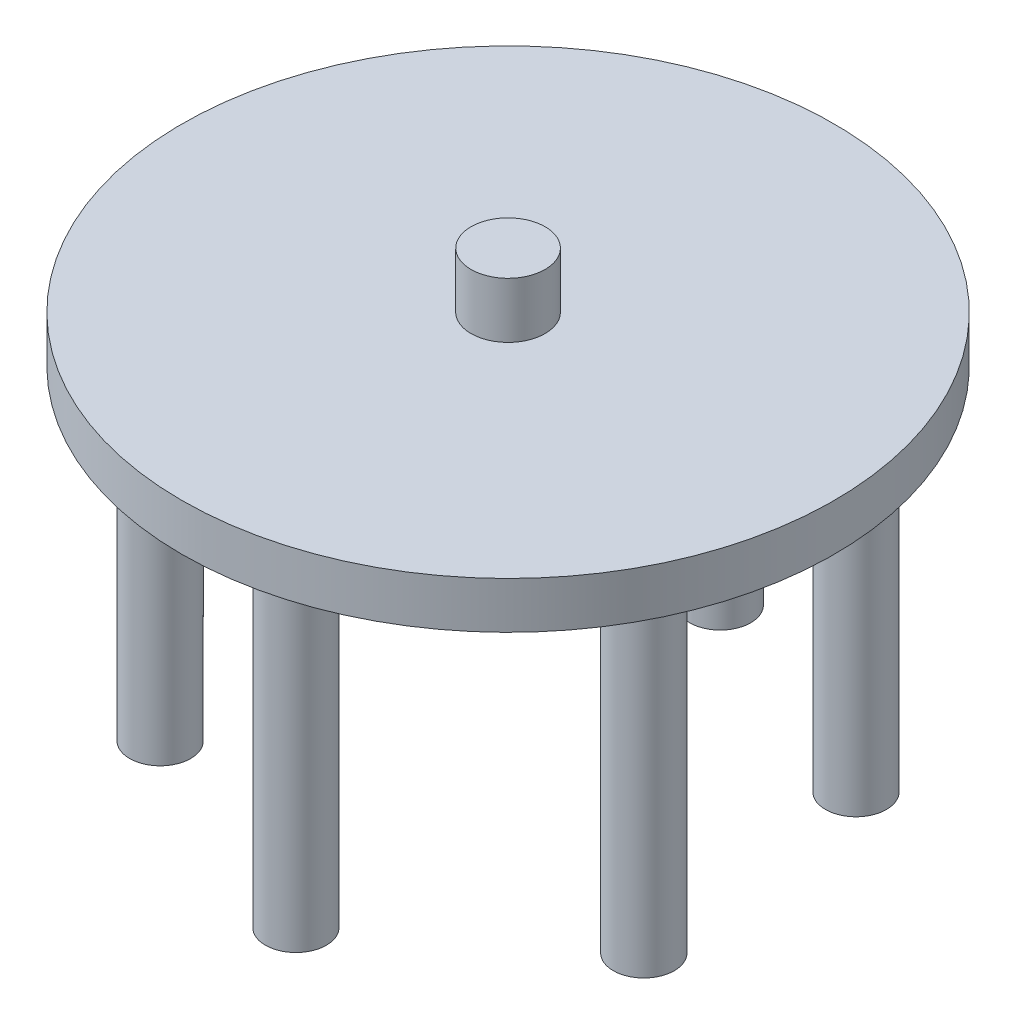
SolidWorks part; units mm, degrees
ref_plane "Front Plane" through (0, 0, 0) normal (0, 0, 1) x (1, 0, 0)
ref_plane "Top Plane" through (0, 0, 0) normal (0, 1, 0) x (1, 0, 0)
ref_plane "Right Plane" through (0, 0, 0) normal (1, 0, 0) x (0, 0, -1)
sketch "Sketch1" plane through (0, 0, 0) normal (0, 1, 0) x (1, 0, 0)
  circle A0 centre (0, 0) radius 27.955
  dimension "D1" = 55.91
extrude "Boss-Extrude1" add sketch "Sketch1" along normal blind 4
sketch "Sketch2" plane through (0, 4, 0) normal (0, 1, 0) x (1, 0, 0)
  circle A0 centre (0, 0) radius 3.175
  dimension "D1" = 6.35
extrude "Boss-Extrude2" add sketch "Sketch2" along normal blind 4.76
sketch "Sketch3" plane through (0, 0, 0) normal (0, -1, 0) x (1, 0, 0)
  circle A0 centre (0, 0) radius 21.2558
  circle A1 centre (2.874, 21.0606) radius 2.6153
  circle A2 centre (19.6761, 8.0413) radius 2.6153
  circle A3 centre (16.802, -13.0193) radius 2.6153
  circle A4 centre (-2.874, -21.0606) radius 2.6153
  circle A5 centre (-19.6761, -8.0413) radius 2.6153
  circle A6 centre (-16.802, 13.0193) radius 2.6153
  point P17 (0, 0)
  dimension "D1" = 6
extrude "Boss-Extrude3" add sketch "Sketch3" along normal blind 29.718 contours A0 A4 | A0 A4 | A0 A3 | A0 A3 | A0 A2 | A0 A2 | A0 A1 | A0 A1 | A0 A6 | A0 A6 | A0 A5 | A0 A5 region at (18.6222, 0, 7.6106) region at (20.6763, 0, 8.4501) region at (17.6561, 0, -13.6811) region at (15.9021, 0, -12.322) region at (2.7201, 0, 19.9327) region at (3.0201, 0, 22.1312) region at (-3.0201, 0, -22.1312) region at (-2.7201, 0, -19.9327) region at (-15.9021, 0, 12.322) region at (-17.6561, 0, 13.6811) region at (-20.6763, 0, -8.4501) region at (-18.6222, 0, -7.6106)
